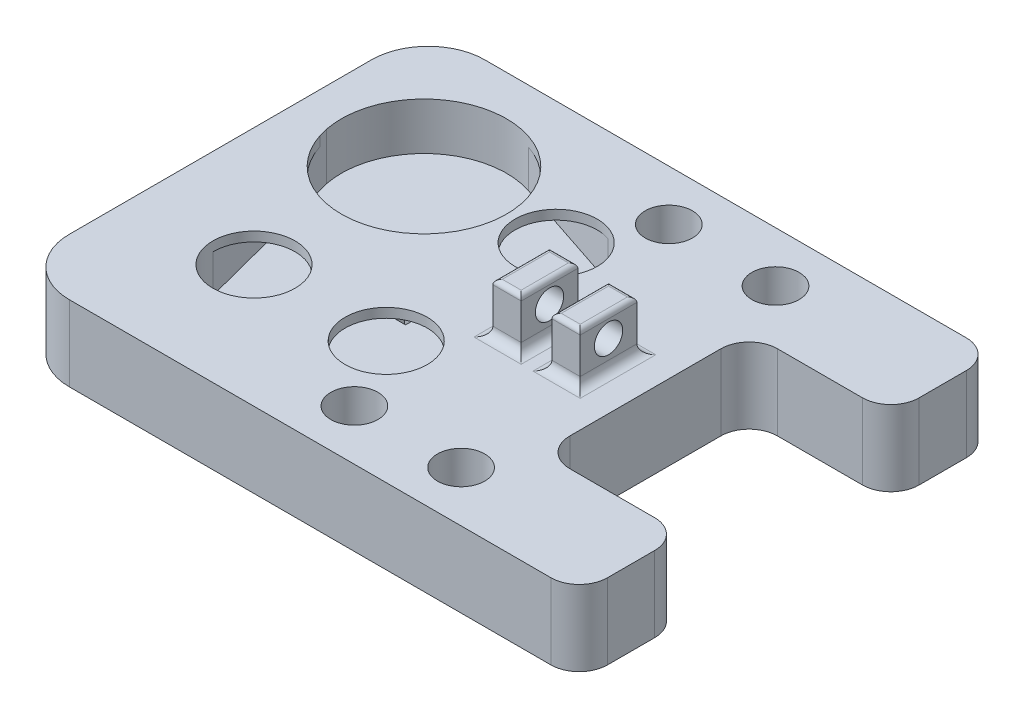
SolidWorks part; units mm, degrees
ref_plane "Front Plane" through (0, 0, 0) normal (0, 0, 1) x (1, 0, 0)
ref_plane "Top Plane" through (0, 0, 0) normal (0, 1, 0) x (1, 0, 0)
ref_plane "Right Plane" through (0, 0, 0) normal (1, 0, 0) x (0, 0, -1)
sketch "Sketch2" plane through (0, 0, 0) normal (0, 1, 0) x (1, 0, 0)
  line L1 (-14.4231, 13.5577) -> (30.5769, 13.5577)
  line L2 (-14.4231, 13.5577) -> (-14.4231, -8.4423)
  line L3 (-14.4231, -8.4423) -> (30.5769, -8.4423)
  line L4 (30.5769, 13.5577) -> (30.5769, -8.4423)
  dimension "D1" = 45
  dimension "D2" = 22
extrude "Boss-Extrude1" add sketch "Sketch2" along normal blind 8
sketch "Sketch3" plane through (0, 0, 0) normal (0, -1, 0) x (1, 0, 0)
  line L0 (30.5769, 8.4423) -> (30.5769, -13.5577) construction
  line L1 (23.5769, -4.0677) -> (3.5769, -4.0677)
  line L2 (23.5769, -4.0677) -> (23.5769, -1.0477)
  line L3 (23.5769, -1.0477) -> (3.5769, -1.0477)
  line L4 (3.5769, -4.0677) -> (3.5769, -1.0477)
  line L5 (-14.4231, -2.5577) -> (30.5769, -2.5577) construction
  line L6 (-14.4231, -13.5577) -> (-14.4231, 8.4423) construction
  dimension "D1" = 20
  dimension "D2" = 7
  dimension "D3" = 3.02
  dimension "D4" = 1.51
extrude "Cut-Extrude1" cut sketch "Sketch3" against normal blind 2
sketch "Sketch4" plane through (0, 0, 0) normal (0, -1, 0) x (1, 0, 0)
  line L0 (3.5769, -1.0477) -> (3.5769, -4.0677) construction
  line L1 (3.5769, -7.5577) -> (-6.4231, -7.5577)
  line L2 (3.5769, -7.5577) -> (3.5769, 2.4423)
  line L3 (3.5769, 2.4423) -> (-6.4231, 2.4423)
  line L4 (-6.4231, -7.5577) -> (-6.4231, -2.5577)
  line L5 (23.5769, -2.5577) -> (-14.4231, -2.5577) construction
  line L7 (23.5769, -4.0677) -> (23.5769, -1.0477) construction
  line L8 (-14.4231, -13.5577) -> (-14.4231, 8.4423) construction
  line L9 (-6.4231, -2.5577) -> (-6.4231, 2.4423)
  dimension "D1" = 10
  dimension "D2" = 10
extrude "Cut-Extrude2" [suppressed] cut sketch "Sketch4" against normal blind 5
sketch "Sketch11" plane through (0, 0, 0) normal (0, -1, 0) x (1, 0, 0)
  circle A0 centre (24.8884, -2.5577) radius 2
  dimension "D1" = 4
extrude "Cut-Extrude4" cut sketch "Sketch11" against normal up to surface (2 mm away) up to face at (13.5769, 2, -2.5577)
sketch "Sketch18" plane through (0, 0, 0) normal (0, -1, 0) x (1, 0, 0)
  line L0 (22.0769, 1.6923) -> (22.0769, -8.4603) construction
  line L4 (30.5769, 8.4423) -> (30.5769, -13.5577) construction
  line L5 (-14.4231, -2.5577) -> (42.1382, -2.5577) construction
  line L6 (-14.4231, -13.5577) -> (-14.4231, 8.4423) construction
  line L7 (2.0769, 1.6923) -> (2.0769, -2.5577) construction
  line L8 (3.3269, -6.8077) -> (3.3269, -2.5577) construction
  circle A0 centre (22.0769, 1.6923) radius 0.6
  circle A1 centre (19.5769, 1.6923) radius 0.6
  circle A2 centre (17.0769, 1.6923) radius 0.6
  circle A3 centre (14.5769, 1.6923) radius 0.6
  circle A4 centre (12.0769, 1.6923) radius 0.6
  circle A5 centre (9.5769, 1.6923) radius 0.6
  circle A6 centre (7.0769, 1.6923) radius 0.6
  circle A7 centre (4.5769, 1.6923) radius 0.6
  circle A8 centre (2.0769, 1.6923) radius 0.6
  circle A9 centre (20.8269, -6.8077) radius 0.6
  circle A10 centre (18.3269, -6.8077) radius 0.6
  circle A11 centre (15.8269, -6.8077) radius 0.6
  circle A12 centre (13.3269, -6.8077) radius 0.6
  circle A13 centre (10.8269, -6.8077) radius 0.6
  circle A14 centre (8.3269, -6.8077) radius 0.6
  circle A15 centre (5.8269, -6.8077) radius 0.6
  circle A16 centre (3.3269, -6.8077) radius 0.6
  dimension "D2" = 1.2
  dimension "D7" = 1.2
  dimension "D3" = 8.5
  dimension "D5" = 1.25
  dimension "D6" = 8.5
  dimension "D1" = 9
  dimension "D8" = 8
sketch "Sketch19" plane through (0, 0, 0) normal (0, -1, 0) x (1, 0, 0)
  line L0 (3.5769, -4.0677) -> (23.5769, -4.0677) construction
  line L5 (3.5769, -1.0477) -> (6.6946, -1.0477)
  line L6 (3.5769, -1.0477) -> (3.5769, -4.0677)
  line L7 (3.5769, -4.0677) -> (6.6946, -4.0677)
  line L8 (6.6946, -1.0477) -> (6.6946, -4.0677)
  dimension "D1" = 3.1177
extrude "Cut-Extrude5" cut sketch "Sketch19" against normal blind 3
sketch "Sketch29" plane through (0, 8, 0) normal (0, 1, 0) x (1, 0, 0)
  line L1 (-14.4231, 13.5577) -> (25.5769, 13.5577)
  line L2 (-14.4231, 13.5577) -> (-14.4231, 24.5577)
  line L3 (-14.4231, 24.5577) -> (25.5769, 24.5577)
  line L4 (25.5769, 13.5577) -> (25.5769, 24.5577)
  line L5 (-14.4231, -8.4423) -> (25.5769, -8.4423)
  line L6 (-14.4231, -8.4423) -> (-14.4231, -19.4423)
  line L7 (-14.4231, -19.4423) -> (25.5769, -19.4423)
  line L8 (25.5769, -8.4423) -> (25.5769, -19.4423)
  dimension "D1" = 40
  dimension "D2" = 11
extrude "Boss-Extrude6" add sketch "Sketch29" against normal up to surface (8 mm away) up to face at (14.4048, 0, -2.5577)
sketch "Sketch21" plane through (0, 3, 0) normal (0, -1, 0) x (1, 0, 0)
  line L0 (3.5769, -2.5577) -> (6.6946, -2.5577) construction
  line L1 (3.5769, -1.0477) -> (3.5769, -4.0677) construction
  line L2 (6.6946, -4.0677) -> (6.6946, -1.0477) construction
  line L3 (5.1358, -1.0477) -> (5.1358, -4.0677) construction
  line L4 (23.5769, -1.0477) -> (3.5769, -1.0477) construction
  line L5 (3.5769, -4.0677) -> (23.5769, -4.0677) construction
  line L6 (19.1358, 15.4423) -> (19.1358, -20.5577)
  line L7 (-10.8642, 15.4423) -> (19.1358, 15.4423)
  line L8 (-10.8642, 15.4423) -> (-10.8642, -20.5577)
  line L9 (-10.8642, -20.5577) -> (19.1358, -20.5577)
  point P12 (5.1358, -2.5577)
  dimension "D1" = 30
  dimension "D2" = 36
  dimension "D3" = 16
extrude "Cut-Extrude8" cut sketch "Sketch21" against normal up to surface (5 mm away) up to face at (16.8269, 8, -2.5577)
sketch "Sketch24" plane through (0, 8, 0) normal (0, 1, 0) x (1, 0, 0)
  line L0 (5.1358, 20.5577) -> (5.1358, -15.4423) construction
  line L1 (-10.8642, -15.4423) -> (-10.8642, 20.5577) construction
  line L3 (-10.8642, 2.5577) -> (21.1358, 2.5577) construction
  line L6 (-1.8642, 11.5577) -> (-1.8642, -6.4423) construction
  line L7 (-10.8642, 20.5577) -> (19.1358, 20.5577)
  line L8 (-10.8642, 20.5577) -> (-10.8642, -15.4423)
  line L9 (-10.8642, -15.4423) -> (19.1358, -15.4423)
  line L10 (19.1358, 20.5577) -> (19.1358, -15.4423)
  line L11 (12.1358, 11.5577) -> (12.1358, -6.4423) construction
  line L13 (12.1358, -6.4423) -> (-1.8642, -6.4423) construction
  line L14 (19.1358, 20.5577) -> (19.1358, -15.4423) construction
  circle A1 centre (12.1358, 11.5577) radius 4.35
  circle A11 centre (-1.8642, 11.5577) radius 8.75
  circle A12 centre (12.1358, -6.4423) radius 4.35
  circle A13 centre (-1.8642, -6.4423) radius 4.35
  point P24 (3.8563, -5.9854)
  point P25 (3.8563, 11.5577)
  point P26 (3.8563, -6.8786)
  point P27 (10.8563, 2.5577)
  point P29 (5.1358, 2.5577)
  dimension "D1" = 8.7
  dimension "D4" = 17.5
  dimension "D2" = 9
  dimension "D3" = 7
  dimension "D5" = 7
  dimension "D6" = 9
  dimension "D7" = 9
  dimension "D8" = 16
extrude "Boss-Extrude3" add sketch "Sketch24" against normal blind 1
sketch "Sketch25" plane through (0, 8, 0) normal (0, 1, 0) x (1, 0, 0)
  line L0 (22.0569, 10.0577) -> (22.0569, -4.9423) construction
  line L1 (20.4319, -0.4423) -> (17.4319, -0.4423)
  line L2 (26.6819, -0.4423) -> (23.6819, -0.4423)
  line L3 (26.6819, -0.4423) -> (26.6819, 5.5577)
  line L4 (26.6819, 5.5577) -> (23.6819, 5.5577)
  line L5 (23.6819, -0.4423) -> (23.6819, 5.5577)
  line L6 (26.6819, -0.4423) -> (23.6819, 5.5577) construction
  line L7 (26.6819, 5.5577) -> (23.6819, -0.4423) construction
  line L8 (20.4319, -0.4423) -> (20.4319, 5.5577)
  line L9 (20.4319, 5.5577) -> (17.4319, 5.5577)
  line L10 (17.4319, -0.4423) -> (17.4319, 5.5577)
  line L11 (20.4319, -0.4423) -> (17.4319, 5.5577) construction
  line L12 (20.4319, 5.5577) -> (17.4319, -0.4423) construction
  line L13 (-14.4231, 2.5577) -> (30.5769, 2.5577) construction
  line L14 (-14.4231, 24.5577) -> (-14.4231, -19.4423) construction
  line L15 (30.5769, -8.4423) -> (30.5769, 13.5577) construction
  circle A0 centre (22.0569, 2.5577) radius 6.2555
  circle A1 centre (22.0569, 2.5577) radius 5.8
  point P6 (22.0569, 2.5577)
  point P7 (25.1819, 2.5577)
  point P16 (18.9319, 2.5577)
  dimension "D1" = 15
  dimension "D2" = 3
  dimension "D3" = 6
  dimension "D4" = 3.125
  dimension "D5" = 3.125
  dimension "D6" = 6
  dimension "D7" = 3
  dimension "D8" = 8.52
extrude "Boss-Extrude4" add sketch "Sketch25" along normal blind 5.3 contours L10 L1 L8 L9 | L5 L2 L3 L4 region at (18.9319, 8, -2.5577) region at (25.1819, 8, -2.5577)
sketch "Sketch26" plane through (26.6819, 0, 0) normal (1, 0, 0) x (0, 0, -1)
  line L0 (2.5577, 13.3) -> (2.5577, 8) construction
  line L1 (-0.4423, 13.3) -> (5.5577, 13.3) construction
  line L2 (-8.4423, 8) -> (13.5577, 8) construction
  line L3 (-0.4423, 8) -> (5.5577, 8) construction
  circle A0 centre (2.5577, 11) radius 1.5
  dimension "D1" = 3
  dimension "D2" = 3
extrude "Cut-Extrude9" cut sketch "Sketch26" against normal up to surface (9.25 mm away) up to face at (17.4319, 10.65, -2.5577)
fillet "Fillet2" radius 1 8 edges at (25.1819, 8, -5.5577) (18.9319, 8, -5.5577) (23.6819, 8, -2.5577) (17.4319, 8, -2.5577) (26.6819, 8, -2.5577) (25.1819, 8, 0.4423) (18.9319, 8, 0.4423) (20.4319, 8, -2.5577)
fillet "Fillet3" radius 0.5 8 edges at (18.9319, 13.3, 0.4423) (20.4319, 13.3, -2.5577) (17.4319, 13.3, -2.5577) (18.9319, 13.3, -5.5577) (25.1819, 13.3, -5.5577) (25.1819, 13.3, 0.4423) (23.6819, 13.3, -2.5577) (26.6819, 13.3, -2.5577)
sketch "Sketch27" plane through (0, 8, 0) normal (0, 1, 0) x (1, 0, 0)
  line L0 (30.5769, 13.5577) -> (25.5769, 13.5577) construction
  line L1 (25.5769, 13.5577) -> (45.5769, 13.5577)
  line L2 (25.5769, 13.5577) -> (25.5769, 24.5577)
  line L3 (25.5769, 24.5577) -> (45.5769, 24.5577)
  line L4 (45.5769, 13.5577) -> (45.5769, 24.5577)
  line L5 (25.5769, 13.5577) -> (25.5769, 24.5577) construction
  dimension "D1" = 20
  dimension "D2" = 11
extrude "Boss-Extrude5" add sketch "Sketch27" against normal up to surface (8 mm away) up to face at (14.4048, 0, -2.5577)
sketch "Sketch28" plane through (0, 8, 0) normal (0, 1, 0) x (1, 0, 0)
  line L0 (16.4169, 19.2077) -> (27.7169, 19.2077) construction
  line L1 (30.5769, -8.4423) -> (30.5769, 13.5577) construction
  line L4 (-14.4231, 24.5577) -> (-14.4231, -19.4423) construction
  circle A0 centre (16.4169, 19.2077) radius 2.5
  circle A1 centre (27.7169, 19.2077) radius 2.5
  point P2 (-14.4231, 2.5577)
  point P3 (28.8391, 19.2077)
  dimension "D1" = 11.3
  dimension "D2" = 5
  dimension "D3" = 16.65
  dimension "D4" = 2.86
extrude "Cut-Extrude10" cut sketch "Sketch28" against normal up to next
ref_plane "Plane1" through (0, 0, -2.5577) normal (0, 0, 1) x (1, 0, 0)
mirror "Mirror1" about plane through (0, 0, -2.5577) normal (0, 0, 1) of "Cut-Extrude10", "Boss-Extrude5"
fillet "Fillet5" radius 6 2 edges at (-14.4231, 4, -24.5577) (-14.4231, 4, 19.4423)
fillet "Fillet6" radius 3 6 edges at (30.5769, 4, 8.4423) (45.5769, 4, -13.5577) (30.5769, 4, -13.5577) (45.5769, 4, 8.4423) (45.5769, 4, -24.5577) (45.5769, 4, 19.4423)
sketch "Sketch30" plane through (0, 8, 0) normal (0, 1, 0) x (1, 0, 0)
  line L4 (19.4085, 23.1759) -> (19.4085, -18.1335)
  line L5 (19.4085, -18.1335) -> (-11.192, -18.1335)
  line L6 (-11.192, -18.1335) -> (-11.192, 23.1759)
  line L7 (-11.192, 23.1759) -> (19.4085, 23.1759)
  line L8 (-1.8642, -10.7923) -> (12.1358, -10.7923)
  line L9 (16.4858, -6.4423) -> (16.4858, 11.5577)
  line L10 (-10.4422, 9.831) -> (-6.2142, -6.4423)
  line L11 (0.8858, 19.8643) -> (13.5029, 15.6873)
  circle A0 centre (16.4169, -14.0923) radius 2.5
  circle A1 centre (16.4169, 19.2077) radius 2.5
  circle A8 centre (-1.8642, -6.4423) radius 4.35 construction
  circle A9 centre (12.1358, -6.4423) radius 4.35 construction
  circle A10 centre (12.1358, 11.5577) radius 4.35 construction
  circle A11 centre (-1.8642, 11.5577) radius 8.75 construction
  arc A12 (0.8858, 19.8643) -> (-10.4422, 9.831) centre (-1.8642, 11.5577) ccw
  arc A13 (16.4858, 11.5577) -> (13.5029, 15.6873) centre (12.1358, 11.5577) ccw
  arc A14 (16.4858, -6.4423) -> (12.1358, -10.7923) centre (12.1358, -6.4423) cw
  arc A15 (-1.8642, -10.7923) -> (-6.2142, -6.4423) centre (-1.8642, -6.4423) cw
extrude "Boss-Extrude7" add sketch "Sketch30" against normal up to surface (5 mm away) up to face at (5.1358, 3, -2.5577)
